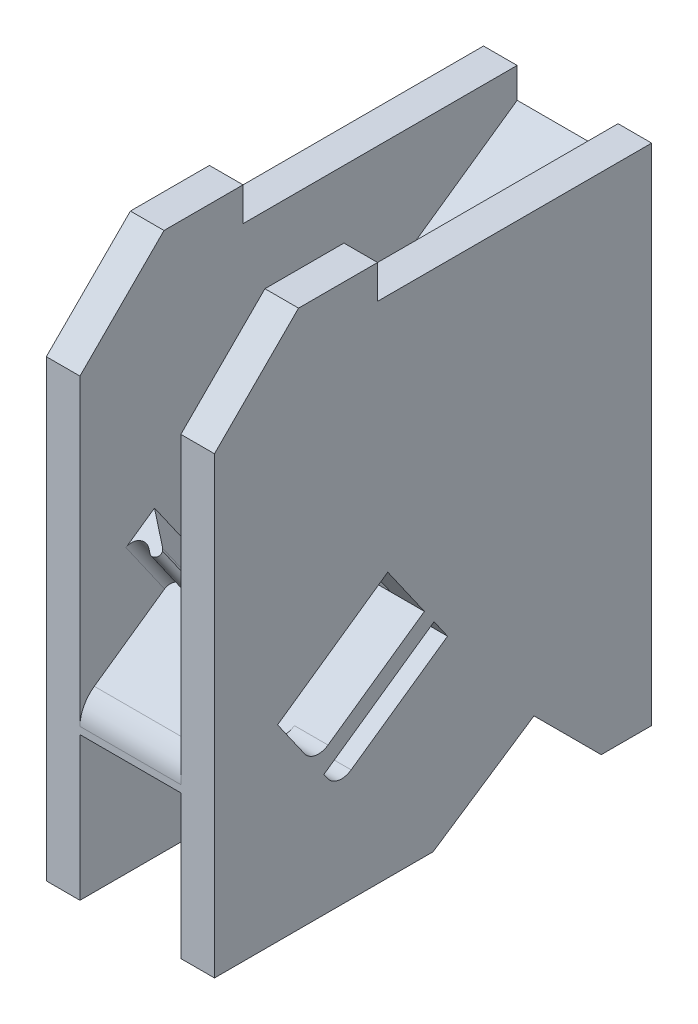
SolidWorks part; units mm, degrees
ref_plane "Front Plane" through (0, 0, 0) normal (0, 0, 1) x (1, 0, 0)
ref_plane "Top Plane" through (0, 0, 0) normal (0, 1, 0) x (1, 0, 0)
ref_plane "Right Plane" through (0, 0, 0) normal (1, 0, 0) x (0, 0, -1)
sketch "Sketch5" plane through (0, 0, 0) normal (0, 1, 0) x (1, 0, 0)
  line L1 (0, 0) -> (50, 0)
  line L2 (0, 0) -> (0, 130)
  line L3 (0, 130) -> (50, 130)
  line L4 (50, 0) -> (50, 130)
  dimension "D1" = 130
  dimension "D2" = 50
extrude "Boss-Extrude1" add sketch "Sketch5" along normal blind 150
sketch "Sketch7" plane through (50, 0, 0) normal (1, 0, 0) x (0, 0, -1)
  line L0 (130, 141.027) -> (0, 50)
  line L1 (115.8456, 131.116) -> (0, 50) construction
  line L2 (0, 150) -> (0, 0) construction
  line L3 (130, 133.7023) -> (0, 42.6754)
  line L4 (119.2871, 126.201) -> (3.4415, 45.0851) construction
  line L5 (130, 150) -> (130, 0) construction
  line L7 (0, 0) -> (130, 0)
  line L8 (130, 0) -> (130, 150)
  line L9 (130, 150) -> (0, 150)
  line L10 (0, 150) -> (0, 0)
  line L11 (0, 0) -> (130, 0)
  line L12 (130, 0) -> (130, 150)
  line L13 (130, 150) -> (0, 150)
  line L14 (0, 150) -> (0, 0)
  point P3 (0, 0)
  point P14 (0, 0)
  point P17 (0, 0)
  line M6 (0, 0) -> (130, 0)
  line M7 (130, 0) -> (130, 150)
  line M8 (130, 150) -> (0, 150)
  line M9 (0, 150) -> (0, 0)
  dimension "D1" = 50
  dimension "D2" = 55
  dimension "D3" = 0
  dimension "D4" = 6
extrude "Cut-Extrude1" cut sketch "Sketch7" against normal mid plane 30 from offset 25 contours L3 M7 M9 M6 | L0 M7 M8 M9 region at (50, 116.4204, -46.9015) region at (50, 48.0093, -76.182) offset against normal yes
ref_plane "Plane2" through (25, 0, 0) normal (-1, 0, 0) x (0, 0, 1)
sketch "Sketch17" plane through (0, 275.4121, -321.9218) normal (0, -0.8192, -0.5736) x (1, 0, 0)
  line L0 (40, 315.183) -> (40, 238.4945) construction
  line L1 (10, 374.2932) -> (40, 374.2932)
  line L2 (10, 374.2932) -> (10, 334.2932)
  line L3 (10, 334.2932) -> (40, 334.2932)
  line L4 (40, 374.2932) -> (40, 334.2932)
  line L6 (10, 315.183) -> (10, 238.4945) construction
  line L8 (10, 234.2932) -> (10, 392.9939) construction
  line L9 (10, 234.2932) -> (40, 234.2932) construction
  point P4 (0, 0)
  point P8 (37.5, 101.061)
  point P9 (37.5, 68.2031)
  point P14 (10, 340.9575)
  dimension "D1" = 40
  dimension "D2" = 100
extrude "Boss-Extrude3" add sketch "Sketch17" against normal blind 5 from offset 30
sketch "Sketch10" plane through (0, 33.5505, 23.4923) normal (0, 0.8192, 0.5736) x (1, 0, 0)
  line L0 (25, 28.6788) -> (25, 172.6872) construction
  line L1 (10, 28.6788) -> (40, 28.6788) construction
  line L2 (50, 86.0365) -> (50, 0) construction
  line L3 (0, 83.1783) -> (50, 83.1783)
  line L4 (0, 83.1783) -> (0, 53.1783)
  line L5 (0, 53.1783) -> (50, 53.1783)
  line L6 (50, 83.1783) -> (50, 53.1783)
  line L7 (0, 83.1783) -> (50, 53.1783) construction
  line L8 (0, 53.1783) -> (50, 83.1783) construction
  line L9 (10, 183.1783) -> (40, 183.1783) construction
  circle A0 centre (25, 68.1783) radius 8.75
  point P4 (25, 68.1783)
  point P9 (0, 0)
  dimension "D1" = 17.5
  dimension "D2" = 30
  dimension "D3" = 100
extrude "Cut-Extrude3" cut sketch "Sketch10" against normal blind 100 contours A0 region at (25, 72.656, -32.3561)
sketch "Sketch18" plane through (0, 0, 0) normal (1, 0, 0) x (0, 0, -1)
  line L0 (130, 150) -> (130, 0) construction
  line L1 (0, 150) -> (48.5, 150)
  line L2 (0, 150) -> (0, 160)
  line L3 (0, 160) -> (48.5, 160)
  line L4 (48.5, 150) -> (48.5, 160)
  dimension "D1" = 81.5
  dimension "D2" = 10
extrude "Boss-Extrude4" add sketch "Sketch18" along normal blind 10
extrude "Boss-Extrude5" add sketch "Sketch18<2>" along normal blind 10 from offset 40
sketch "Sketch18<2>" plane through (0, 0, 0) normal (1, 0, 0) x (0, 0, -1) same geometry as "Sketch18"
chamfer "Chamfer1" distance 25 angle 45 2 edges at (5, 160, 0) (45, 160, 0)
sketch "Sketch21" plane through (0, 0, 0) normal (1, 0, 0) x (0, 0, -1)
  line L0 (62.4242, 63.1905) -> (29.6581, 40.2475)
  line L1 (62.4242, 63.1905) -> (51.5263, 78.7544)
  line L2 (29.6581, 40.2475) -> (18.7602, 55.8114)
  line L3 (51.5263, 78.7544) -> (18.7602, 55.8114)
  line L4 (130, 133.7023) -> (0, 42.6754) construction
  line L5 (65.2921, 59.0948) -> (32.526, 36.1517)
  line L6 (65.2921, 59.0948) -> (32.526, 36.1517)
  line L7 (65.2921, 59.0948) -> (69.3071, 53.3607)
  line L8 (32.526, 36.1517) -> (36.541, 30.4177)
  line L9 (69.3071, 53.3607) -> (36.541, 30.4177)
  dimension "D1" = 90
  dimension "D3" = 7
  dimension "D2" = 5
extrude "Cut-Extrude5" cut sketch "Sketch21" along normal blind 70 contours L1 L3 L2 L0 | L9 L7 L5 L8 region at (0, 59.501, -40.5922) region at (0, 44.7562, -50.9166)
fillet "Fillet1" radius 5 4 edges at (5, 30.4177, -36.541) (45, 30.4177, -36.541) (5, 40.2475, -29.6581) (45, 40.2475, -29.6581)
sketch "Sketch22" plane through (0, 0, 0) normal (-1, 0, 0) x (0, 0, 1)
  line L0 (-115, 0) -> (-95, 20)
  line L1 (-130, 0) -> (0, 0) construction
  line L3 (-95, 20) -> (-65, 0)
  line L4 (-115, 0) -> (-65, 0)
  dimension "D1" = 20
  dimension "D2" = 20
  dimension "D3" = 15
  dimension "D4" = 65
extrude "Cut-Extrude6" cut sketch "Sketch22" against normal blind 70
fillet "Fillet2" radius 10 1 edges at (25, 50, 0)
sketch "Sketch23" plane through (0, 33.5505, 23.4923) normal (0, 0.8192, 0.5736) x (1, 0, 0)
  line L0 (-9.6382, 68.1783) -> (71.6348, 68.1783) construction
  line L1 (-9.6382, 63.1783) -> (85.0275, 63.1783) construction
  line L2 (32.1807, 63.1783) -> (40, 69.7394)
  line L3 (40, 187.3795) -> (40, 33.8845) construction
  line L4 (25, 68.1783) -> (25, 92.3432) construction
  line L5 (34.1091, 60.8801) -> (41.9284, 67.4413)
  line L6 (40, 69.7394) -> (40, 61.5525)
  line L7 (10, 69.7394) -> (10, 61.5525)
  line L8 (15.8909, 60.8801) -> (8.0716, 67.4413)
  line L9 (17.8193, 63.1783) -> (10, 69.7394)
  circle A0 centre (25, 68.1783) radius 8.75 construction
  circle A1 centre (25, 68.1783) radius 8.75
  arc A2 (32.1807, 63.1783) -> (34.1091, 60.8801) centre (33.1449, 62.0292) ccw
  arc A3 (17.8193, 63.1783) -> (15.8909, 60.8801) centre (16.8551, 62.0292) cw
  point P7 (32.1807, 63.1783)
  point P8 (17.8193, 63.1783)
  circle M8 centre (25, 68.1783) radius 8.75
  line M9 (10, 187.3795) -> (10, 33.8845)
  line M11 (40, 33.8845) -> (40, 187.3795)
  dimension "D1" = 5
  dimension "D2" = 50
  dimension "D3" = 3
extrude "Boss-Extrude6" add sketch "Sketch23" along normal blind 20 contours A2 L5 L2 M8 M11 | A3 L9 L8 M8 M9 region at (36.0997, 70.597, -29.4155) region at (13.9003, 70.597, -29.4155)
fillet "Fillet4" radius 3 2 edges at (40, 79.4967, -24.6911) (10, 79.4967, -24.6911)
